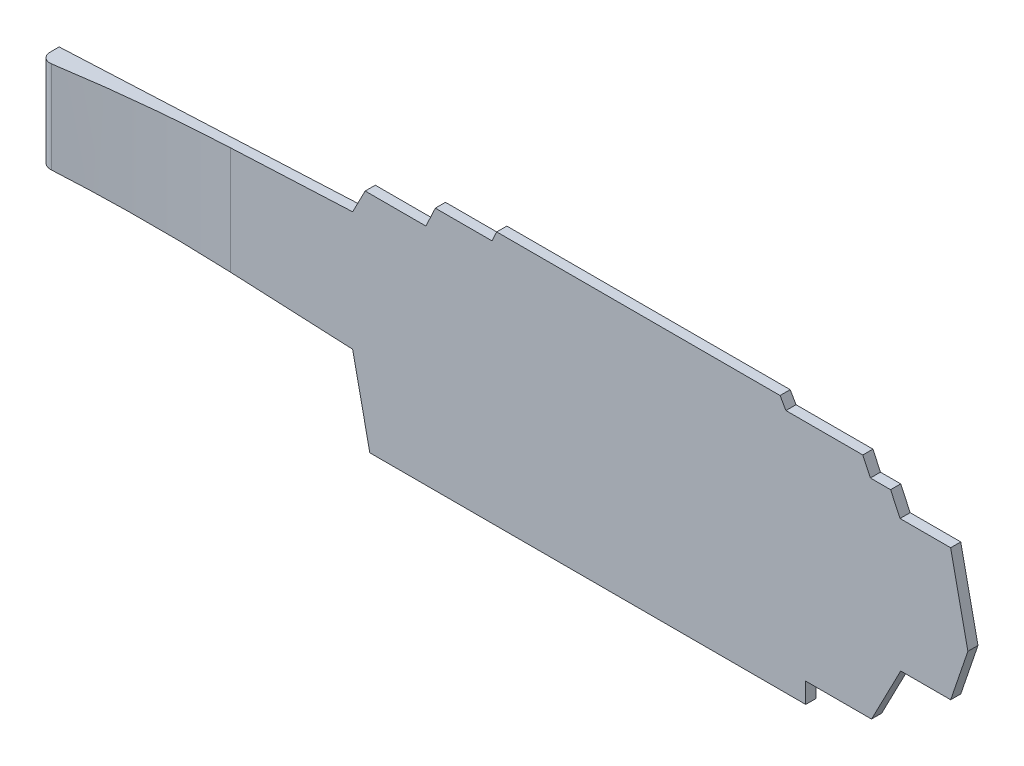
SolidWorks part; units mm, degrees
ref_plane "前视基准面" through (0, 0, 0) normal (0, 0, 1) x (1, 0, 0)
ref_plane "上视基准面" through (0, 0, 0) normal (0, 1, 0) x (1, 0, 0)
ref_plane "右视基准面" through (0, 0, 0) normal (1, 0, 0) x (0, 0, -1)
other "Configuration Table"
sketch "草图1" plane through (0, 0, 0) normal (0, 0, 1) x (1, 0, 0)
  line L0 (0, 0) -> (2500, 0) construction
  line L1 (0, 0) -> (0, 225)
  line L2 (0, 225) -> (1500, 294.39)
  line L3 (1500, 294.39) -> (1562.073, 414.39)
  line L4 (1562.073, 414.39) -> (1862.073, 414.39)
  line L5 (1862.073, 414.39) -> (1908.7037, 514.39)
  line L6 (1908.7037, 514.39) -> (2188.7037, 514.39)
  line L7 (2188.7037, 514.39) -> (2212.0191, 564.39)
  line L8 (2212.0191, 564.39) -> (3612.0191, 564.39)
  line L9 (3612.0191, 564.39) -> (3640.8866, 514.39)
  line L10 (3640.8866, 514.39) -> (4020.8866, 514.39)
  line L11 (4020.8866, 514.39) -> (4058.1912, 434.39)
  line L12 (4058.1912, 434.39) -> (4158.1912, 434.39)
  line L13 (4158.1912, 434.39) -> (4204.822, 334.39)
  line L14 (4204.822, 334.39) -> (4454.822, 334.39)
  line L15 (4454.822, 334.39) -> (4539.9896, -66.2918)
  line L16 (4539.9896, -66.2918) -> (4454.9696, -316.2918)
  line L17 (4454.9696, -316.2918) -> (4208.14, -316.2918)
  line L18 (4208.14, -316.2918) -> (4063.94, -594.39)
  line L19 (4063.94, -594.39) -> (3738.77, -594.39)
  line L20 (3738.77, -594.39) -> (3738.77, -694.39)
  line L21 (3738.77, -694.39) -> (1585.02, -694.39)
  line L22 (1585.02, -694.39) -> (1500, -293.6768)
  line L23 (1500, -293.6768) -> (0, -224.2868)
  line L24 (0, -224.2868) -> (0, 0)
  line L25 (4454.822, 334.39) -> (1500, -293.6768) construction
  line L26 (1585.02, -694.39) -> (4539.9896, -66.2918) construction
  dimension "D1" = 225
  dimension "D2" = 120
  dimension "D3" = 100
  dimension "D4" = 50
  dimension "D5" = 120
  dimension "D6" = 115
  dimension "D7" = 1400
  dimension "D8" = 69.39
  dimension "D9" = 1500
  dimension "D10" = 1500
  dimension "D11" = 380
  dimension "D12" = 100
  dimension "D13" = 250
  dimension "D14" = 120
  dimension "D15" = 115
  dimension "D16" = 115
  dimension "D17" = 50
  dimension "D18" = 80
  dimension "D19" = 100
  dimension "D20" = 300
  dimension "D21" = 280
  dimension "D22" = 85.02
  dimension "D23" = 2153.75
  dimension "D24" = 325.17
  dimension "D25" = 144.2
  dimension "D26" = 85.02
  dimension "D27" = 564.39
  dimension "D28" = 12
  dimension "D29" = 250
  dimension "D30" = 90
  dimension "D31" = 694.39
  dimension "D32" = 100
extrude "凸台-拉伸1" add sketch "草图1" along normal blind 50
sketch "草图2" plane through (0, 0, 50) normal (0, 0, 1) x (1, 0, 0)
  line L0 (0, 225) -> (1500, 294.39)
  line L1 (1500, 294.39) -> (1500, -293.6768)
  line L2 (1500, -293.6768) -> (0, -224.2868)
  line L3 (0, -224.2868) -> (0, 225)
extrude "凸台-拉伸3" add sketch "草图2" along normal blind 50
sketch "草图8" plane through (0, 0, 0) normal (0, 1, 0) x (1, 0, 0)
  line L0 (1500, -50) -> (897.23, -50)
  line L1 (0, -100) -> (0, 0) construction
  line L2 (0, -100) -> (1500, -100) construction
  line L3 (1500, -50) -> (1500, -286.1525)
  line L4 (1500, -286.1525) -> (0, -100)
  arc A0 (897.23, -50) -> (0, -100) centre (897.23, -8125.2167) ccw
  dimension "D1" = 602.77
extrude "切除-拉伸2" cut sketch "草图8" against normal through all both and the other way through all
fillet "圆角4" radius 50 1 edges at (0, 0.3566, 100)
sketch "草图9" plane through (0, 0, 0) normal (0, 0, 1) x (1, 0, 0)
  line L0 (0, -224.2868) -> (1500, -293.6768)
  line L1 (0, 225) -> (0, -224.2868) construction
  line L2 (0, -224.2868) -> (1500, -293.6768) construction
  line L3 (1500, -293.6768) -> (4350, -293.6768)
  line L4 (4350, -293.6768) -> (4350, 294.39)
  line L5 (4350, 294.39) -> (1500, 294.39)
  line L6 (1500, 294.39) -> (0, 225)
  line L7 (0, 225) -> (0, -224.2868)
  dimension "D1" = 2850
ref_plane "基准面1" through (0, 0, -250) normal (0, 0, -1) x (-1, 0, 0)
